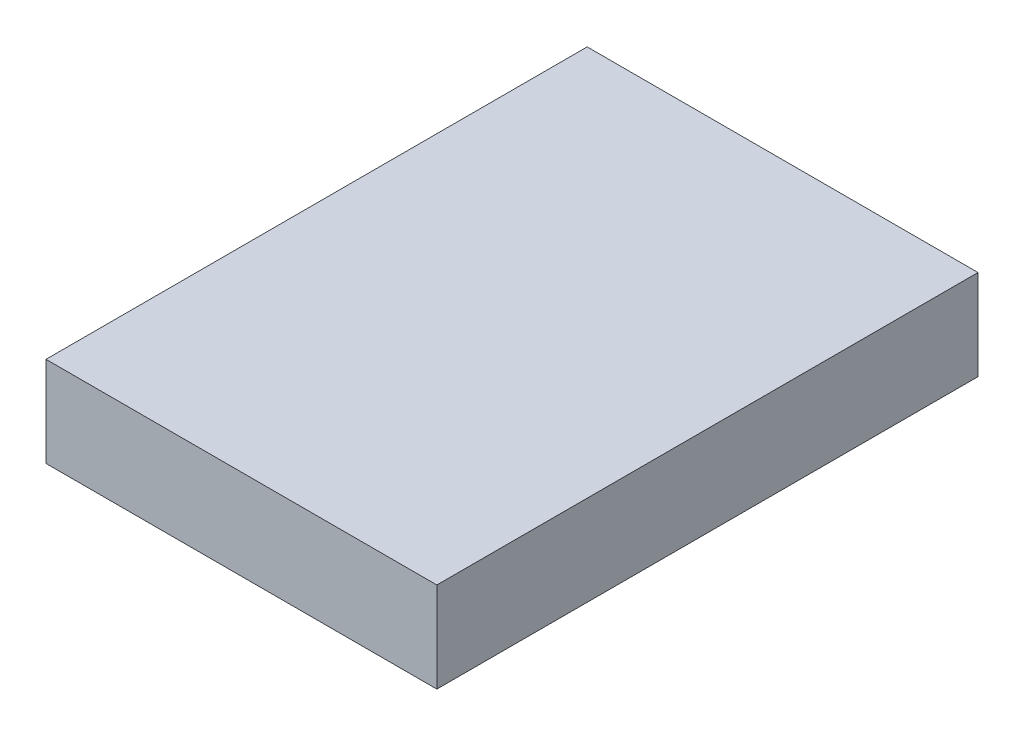
SolidWorks part; units mm, degrees
material "Polyurethane Foam Rigid"
ref_plane "X-Y Datum" through (0, 0, 0) normal (0, 0, 1) x (1, 0, 0)
ref_plane "X-Z Datum" through (0, 0, 0) normal (0, 1, 0) x (1, 0, 0)
ref_plane "Y-Z Datum" through (0, 0, 0) normal (1, 0, 0) x (0, 0, -1)
sketch "Sketch1" plane through (0, 0, 0) normal (0, 0, 1) x (1, 0, 0)
  line L1 (-82.55, -19.05) -> (82.55, -19.05)
  line L2 (-82.55, -19.05) -> (-82.55, 19.05)
  line L3 (-82.55, 19.05) -> (82.55, 19.05)
  line L4 (82.55, -19.05) -> (82.55, 19.05)
  line L5 (-82.55, -19.05) -> (82.55, 19.05) construction
  line L6 (-82.55, 19.05) -> (82.55, -19.05) construction
  point P0 (0, 0)
  dimension "D1" = 38.1
  dimension "D2" = 165.1
extrude "Boss-Extrude1" add sketch "Sketch1" along normal blind 228.6
